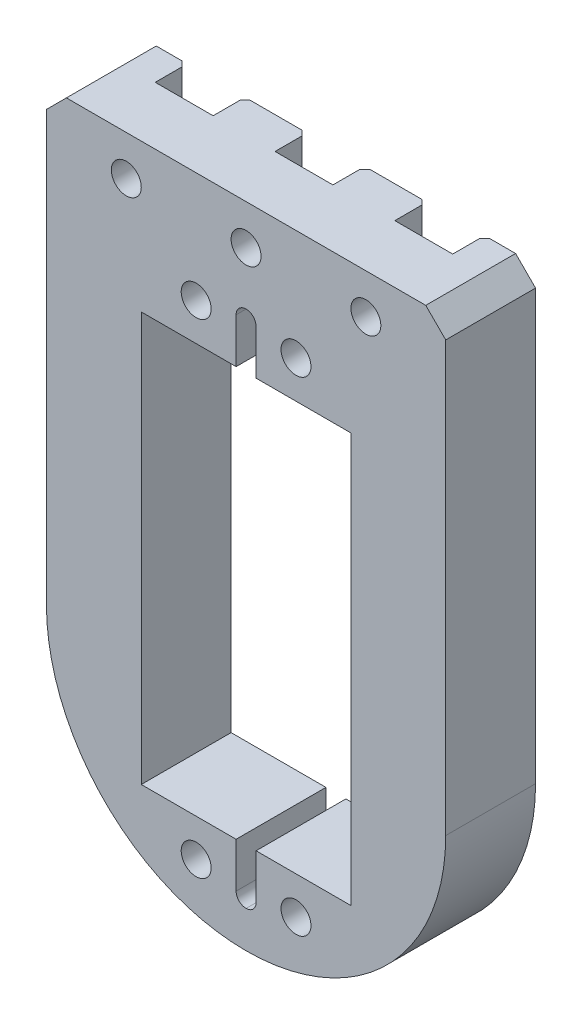
SolidWorks part; units mm, degrees
ref_plane "前视基准面" through (0, 0, 0) normal (0, 0, 1) x (1, 0, 0)
ref_plane "上视基准面" through (0, 0, 0) normal (0, 1, 0) x (1, 0, 0)
ref_plane "右视基准面" through (0, 0, 0) normal (1, 0, 0) x (0, 0, -1)
other "Configuration Table"
sketch "草图1" plane through (0, 0, 0) normal (0, 0, 1) x (1, 0, 0)
  line L1 (0, -5) -> (40, -5)
  line L2 (0, -5) -> (0, -70)
  line L3 (0, -70) -> (40, -70)
  line L4 (40, -5) -> (40, -70)
  dimension "D1" = 40
  dimension "D2" = 65
extrude "凸台-拉伸1" add sketch "草图1" along normal blind 9
chamfer "倒角1" distance 2 angle 45 2 edges at (40, -5, 4.5) (0, -5, 4.5)
fillet "圆角3" radius 20 2 edges at (0, -70, 4.5) (40, -70, 4.5)
sketch "草图2" plane through (0, 0, 0) normal (0, 0, -1) x (-1, 0, 0)
  line L0 (0, -7) -> (0, -50) construction
  line L1 (-30.5, -19.82) -> (-9.5, -19.82)
  line L2 (-30.5, -19.82) -> (-30.5, -60.82)
  line L3 (-30.5, -60.82) -> (-9.5, -60.82)
  line L4 (-9.5, -19.82) -> (-9.5, -60.82)
  line L5 (-30.5, -19.82) -> (-9.5, -60.82) construction
  line L6 (-30.5, -60.82) -> (-9.5, -19.82) construction
  point P0 (-20, -40.32)
  dimension "D1" = 21
  dimension "D2" = 41
  dimension "D3" = 20
  dimension "D4" = 29.68
extrude "切除-拉伸1" cut sketch "草图2" against normal blind 10
sketch "草图3" plane through (0, 0, 9) normal (0, 0, 1) x (1, 0, 0)
  line L0 (19, -14.32) -> (21, -14.32)
  line L1 (19, -14.32) -> (19, -19.82)
  line L2 (19, -19.82) -> (21, -19.82)
  line L3 (21, -14.32) -> (21, -19.82)
  line L4 (19, -14.32) -> (21, -19.82) construction
  line L5 (19, -19.82) -> (21, -14.32) construction
  line L6 (19, -60.82) -> (19, -66.32)
  line L7 (19, -60.82) -> (21, -60.82)
  line L8 (21, -60.82) -> (21, -66.32)
  line L9 (19, -66.32) -> (21, -66.32)
  line L10 (30.5, -19.82) -> (9.5, -19.82) construction
  line L11 (9.5, -19.82) -> (9.5, -60.82) construction
  line L12 (9.5, -60.82) -> (30.5, -60.82) construction
  point P0 (20, -17.07)
  dimension "D1" = 2
  dimension "D2" = 0
  dimension "D3" = 10.5
  dimension "D4" = 0
  dimension "D5" = 9.5
  dimension "D6" = 5.5
  dimension "D7" = 5.5
  dimension "D8" = 2
extrude "切除-拉伸2" cut sketch "草图3" against normal blind 10
sketch "草图4" plane through (0, 0, 0) normal (0, 0, -1) x (-1, 0, 0)
  line L0 (-21, -19.82) -> (-21, -14.32) construction
  line L1 (-21, -19.82) -> (-30.5, -19.82) construction
  circle A0 centre (-25, -16.07) radius 1.5
  circle A1 centre (-15, -16.07) radius 1.5
  circle A2 centre (-25, -64.57) radius 1.5
  circle A3 centre (-15, -64.57) radius 1.5
  dimension "D1" = 3
  dimension "D2" = 4
  dimension "D3" = 3.75
  dimension "D4" = 2
  dimension "D5" = 2
extrude "切除-拉伸3" cut sketch "草图4" against normal blind 10
sketch "草图5" plane through (0, 0, 0) normal (0, 0, -1) x (-1, 0, 0)
  line L0 (-38, -5) -> (-2, -5) construction
  line L1 (-40, -50) -> (-40, -7) construction
  circle A0 centre (-32, -9) radius 1.5
  circle A1 centre (-20, -9) radius 1.5
  circle A2 centre (-8, -9) radius 1.5
  dimension "D1" = 3
  dimension "D3" = 8
  dimension "D2" = 4
  dimension "D4" = 2
  dimension "D5" = 2
extrude "切除-拉伸4" cut sketch "草图5" against normal blind 10
fillet "圆角4" radius 1 4 edges at (21, -66.32, 4.5) (19, -66.32, 4.5) (21, -14.32, 4.5) (19, -14.32, 4.5)
sketch "草图7" plane through (0, 0, 0) normal (0, 0, -1) x (-1, 0, 0)
  line L0 (-38, -5) -> (-2, -5) construction
  line L2 (-34.9, -9) -> (-34.9, -5)
  line L3 (-34.9, -5) -> (-29.1, -5)
  line L4 (-29.1, -9) -> (-29.1, -5)
  line L5 (-17.1, -9) -> (-17.1, -5)
  line L6 (-22.9, -5) -> (-17.1, -5)
  line L7 (-22.9, -9) -> (-22.9, -5)
  line L8 (-5.1, -9) -> (-5.1, -5)
  line L9 (-10.9, -5) -> (-5.1, -5)
  line L10 (-10.9, -9) -> (-10.9, -5)
  arc A0 (-34.9, -9) -> (-29.1, -9) centre (-32, -9) ccw
  arc A1 (-22.9, -9) -> (-17.1, -9) centre (-20, -9) ccw
  arc A2 (-10.9, -9) -> (-5.1, -9) centre (-8, -9) ccw
  dimension "D1" = 5.8
  dimension "D2" = 5.8
  dimension "D3" = 3
extrude "切除-拉伸5" cut sketch "草图7" against normal blind 3.2
chamfer "倒角2" distance 0.5 angle 45 13 edges at (13.5, -64.57, 0) (23.5, -64.57, 0) (13.5, -16.07, 0) (23.5, -16.07, 0) (5.1, -7, 0) (8, -11.9, 0) (10.9, -7, 0) (17.1, -7, 0) (20, -11.9, 0) (22.9, -7, 0) (29.1, -7, 0) (32, -11.9, 0) (34.9, -7, 0)
